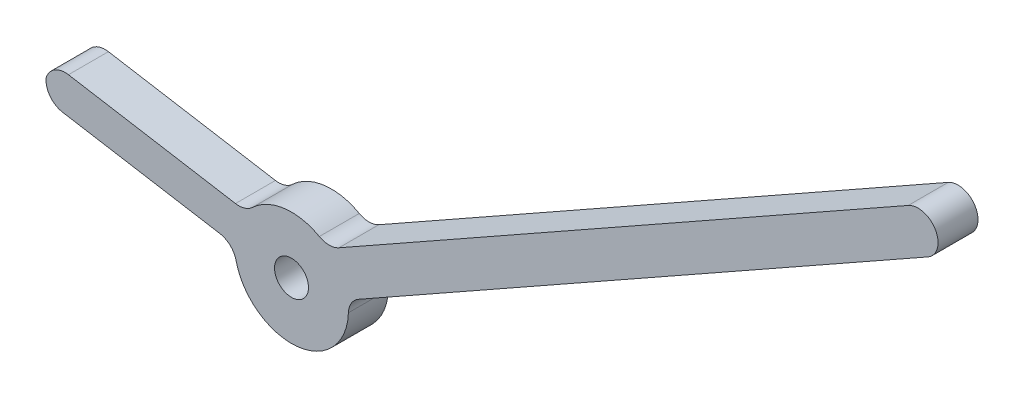
SolidWorks part; units mm, degrees
ref_plane "Front Plane" through (0, 0, 0) normal (0, 0, 1) x (1, 0, 0)
ref_plane "Top Plane" through (0, 0, 0) normal (0, 1, 0) x (1, 0, 0)
ref_plane "Right Plane" through (0, 0, 0) normal (1, 0, 0) x (0, 0, -1)
sketch "Sketch1" plane through (0, 0, 0) normal (0, 0, 1) x (1, 0, 0)
  line L0 (-1000, 0) -> (49000, 0) construction
  line L1 (17.9605, 17.9605) -> (0, 0) construction
  line L2 (-23.3808, 9.9246) -> (0, 0) construction
  circle A0 centre (0, 0) radius 2.159
  circle A2 centre (0, 0) radius 31.877
  arc A3 (17.9605, 17.9605) -> (-23.3808, 9.9246) centre (0, 0) ccw construction
  arc A4 (19.4872, 19.4872) -> (-25.3682, 10.7682) centre (0, 0) ccw
  arc A5 (16.4339, 16.4339) -> (-21.3935, 9.081) centre (0, 0) ccw
  arc A6 (16.4339, 16.4339) -> (19.4872, 19.4872) centre (17.9605, 17.9605) ccw
  arc A7 (-25.3682, 10.7682) -> (-21.3935, 9.081) centre (-23.3808, 9.9246) ccw
  point P6 (-4.8465, 24.9333)
  dimension "D1" = 25.4
  dimension "D2" = 2.159
  dimension "D5" = 4.318
  dimension "D6" = 4.318
  dimension "D3" = 45
  dimension "D4" = 112
extrude "Boss-Extrude1" add sketch "Sketch1" along normal blind 5.08
sketch "Sketch2" plane through (0, 0, 5.08) normal (0, 0, 1) x (1, 0, 0)
  line L0 (0, 0) -> (17.9605, 17.9605) construction
  line L3 (-1000, 0) -> (49000, 0) construction
  line L4 (17.9605, 17.9605) -> (46.6973, 46.6973) construction
  line L7 (46.6973, 46.6973) -> (79.6721, 44.9692) construction
  line L8 (0, 0) -> (79.6721, 44.9692)
  line L9 (1.2485, -2.212) -> (80.9206, 42.7572)
  line L10 (-1.2485, 2.212) -> (78.4236, 47.1812)
  arc A0 (1.2485, -2.212) -> (-1.2485, 2.212) centre (0, 0) cw
  arc A1 (80.9206, 42.7572) -> (78.4236, 47.1812) centre (79.6721, 44.9692) ccw
  circle M3 centre (0, 0) radius 31.877
  dimension "D3" = 132
  dimension "D4" = 2.54
  dimension "D1" = 40.64
  dimension "D2" = 33.02
  dimension "D5" = 2.54
extrude "Boss-Extrude4" add sketch "Sketch2" against normal blind 5.08 contours L10 M3 region at (28.9448, 14.8478, 5.08)
sketch "Sketch6" plane through (0, 0, 5.08) normal (0, 0, 1) x (1, 0, 0)
  line L0 (-5.7612, 4.3832) -> (-30.7021, 8.5748)
  line L1 (4.6548, 5.544) -> (26.4235, 17.8309)
  line L2 (28.9205, 13.4069) -> (7.1518, 1.12)
  line L3 (28.9205, 13.4069) -> (80.9206, 42.7572) construction
  line L4 (-7.239, 0) -> (-31.6127, 4.0963)
  line L7 (28.9205, 13.4069) -> (80.9206, 42.7572)
  line L8 (78.4236, 47.1812) -> (26.4235, 17.8309)
  line L9 (28.9205, 13.4069) -> (80.9206, 42.7572)
  line L10 (78.4236, 47.1812) -> (26.4235, 17.8309)
  circle A4 centre (0, 0) radius 7.239
  circle A5 centre (0, 0) radius 7.239
  arc A6 (26.4235, 17.8309) -> (28.9205, 13.4069) centre (0, 0) ccw construction
  arc A8 (-25.3682, 10.7682) -> (-21.3935, 9.081) centre (-23.3808, 9.9246) ccw construction
  arc A11 (26.4235, 17.8309) -> (28.9205, 13.4069) centre (0, 0) ccw
  arc A12 (80.9206, 42.7572) -> (78.4236, 47.1812) centre (79.6721, 44.9692) ccw
  arc A13 (26.4235, 17.8309) -> (28.9205, 13.4069) centre (0, 0) ccw
  arc A14 (80.9206, 42.7572) -> (78.4236, 47.1812) centre (79.6721, 44.9692) ccw
  point P16 (4.9485, 5.2836)
  point P24 (-6.5506, 4.0963)
  arc M5 (26.4235, 17.8309) -> (28.9205, 13.4069) centre (0, 0) ccw
  arc M10 (-25.3682, 10.7682) -> (19.4872, 19.4872) centre (0, 0) cw
  arc M11 (19.4872, 19.4872) -> (16.4339, 16.4339) centre (17.9605, 17.9605) cw
  arc M12 (16.4339, 16.4339) -> (-21.3935, 9.081) centre (0, 0) ccw
  arc M13 (-21.3935, 9.081) -> (-25.3682, 10.7682) centre (-23.3808, 9.9246) cw
  dimension "D2" = 7.112
  dimension "D4" = 2.5445
  dimension "D1" = 5.08
  dimension "D3" = 0
extrude "Cut-Extrude1" cut sketch "Sketch6" against normal through all both and the other way through all contours A5 L4 L2 M5 | A5 L1 L0 M5 M13 M10 M11 M12 region at (-2.4742, 17.2726, 5.08) region at (1.6833, -11.6773, 5.08)
fillet "Fillet1" radius 2.54 6 edges at (-31.6127, 4.0963, 2.54) (-30.7021, 8.5748, 2.54) (7.1518, 1.12, 2.54) (-7.239, 0, 2.54) (-5.7612, 4.3832, 2.54) (4.6548, 5.544, 2.54)
